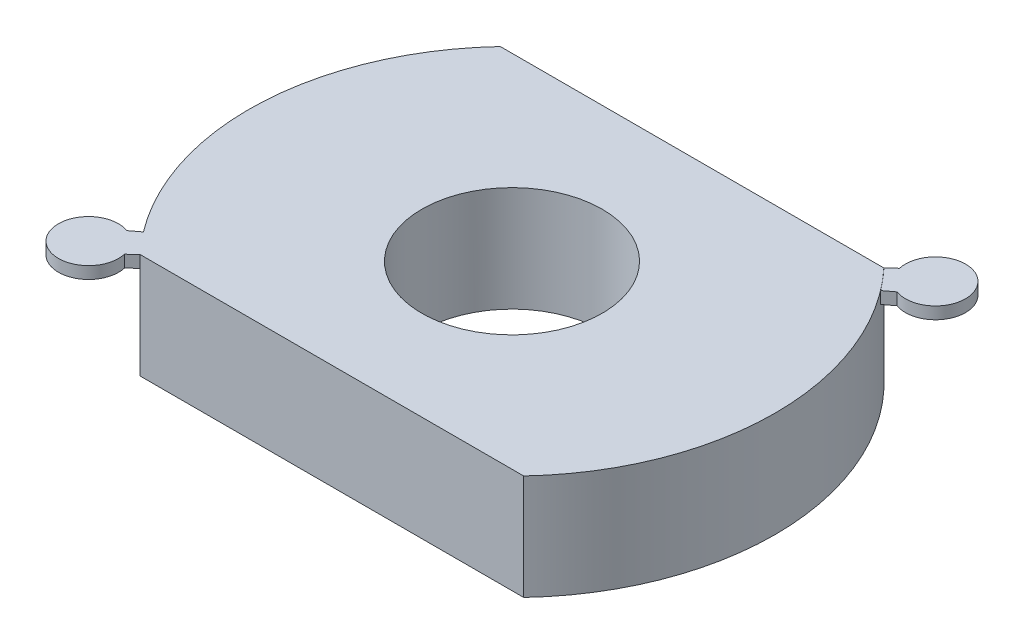
SolidWorks part; units mm, degrees
material "1345 Alloy"
ref_plane "Front Plane" through (0, 0, 0) normal (0, 0, 1) x (1, 0, 0)
ref_plane "Top Plane" through (0, 0, 0) normal (0, 1, 0) x (1, 0, 0)
ref_plane "Right Plane" through (0, 0, 0) normal (1, 0, 0) x (0, 0, -1)
sketch "Sketch1" plane through (0, 0, 0) normal (0, 1, 0) x (1, 0, 0)
  line L0 (-1712.4333, 578.2677) -> (-1658.0172, 559.892) construction
  line L1 (-1682.6566, 611.2885) -> (-1644.8226, 597.5438) construction
  line L2 (-1769.951, 660.0706) -> (-1712.4333, 741.8735) construction
  circle A0 centre (0, 0) radius 1750
  arc A3 (-1712.4333, 578.2677) -> (-1712.4333, 741.8735) centre (-1769.951, 660.0706) cw construction
  arc A4 (-1712.4333, 741.8735) -> (-1682.6566, 611.2885) centre (-1769.951, 660.0706) cw construction
extrude "Boss-Extrude1" add sketch "Sketch1" along normal blind 700
sketch "Sketch9" plane through (0, 0, 0) normal (0, -1, 0) x (1, 0, 0)
  line L1 (-2106.3119, -1198.0599) -> (2106.3119, -1198.0599)
  line L2 (-2106.3119, -1198.0599) -> (-2106.3119, 1198.0599)
  line L3 (-2106.3119, 1198.0599) -> (2106.3119, 1198.0599)
  line L4 (2106.3119, -1198.0599) -> (2106.3119, 1198.0599)
  line L5 (-2106.3119, -1198.0599) -> (2106.3119, 1198.0599) construction
  line L6 (-2106.3119, 1198.0599) -> (2106.3119, -1198.0599) construction
  line L7 (-2636.6179, -2082.9122) -> (2636.6179, -2082.9122)
  line L8 (-2636.6179, -2082.9122) -> (-2636.6179, 2082.9122)
  line L9 (-2636.6179, 2082.9122) -> (2636.6179, 2082.9122)
  line L10 (2636.6179, -2082.9122) -> (2636.6179, 2082.9122)
  line L11 (-2636.6179, -2082.9122) -> (2636.6179, 2082.9122) construction
  line L12 (-2636.6179, 2082.9122) -> (2636.6179, -2082.9122) construction
  point P0 (0, 0)
  point P6 (0, 0)
extrude "Cut-Extrude10" cut sketch "Sketch9" against normal through all both and the other way through all
sketch "Sketch3" plane through (0, 0, 0) normal (0, -1, 0) x (1, 0, 0)
  circle A0 centre (0, 0) radius 600
extrude "Cut-Extrude3" cut sketch "Sketch3" against normal through all both and the other way through all
shell "Shell1" thickness 1.5 removed face at (0, 0, 600)
sketch "Sketch12" plane through (0, 700, 0) normal (0, 1, 0) x (1, 0, 0)
  line L0 (-1275.7204, -1197.9305) -> (-1329.4274, -1248.3625)
  line L1 (-1275.7204, -1197.9305) -> (-1329.4274, -1248.3625)
  line L2 (-1456.8867, -1104.0663) -> (-1394.7434, -1056.9725)
  line L3 (-1212.6439, -1163.1539) -> (-1394.7434, -1056.9725) construction
  line L4 (-1329.4274, -1248.3625) -> (-1275.8583, -1198.0599) construction
  line L5 (1275.5989, -1198.0599) -> (-1275.5989, -1198.0599) construction
  line L6 (-1275.5989, 1198.0599) -> (1275.5989, -1198.0599) construction
  line L7 (0, 0) -> (-1750, 0) construction
  line L13 (0, 0) -> (0, 1750) construction
  line L14 (1212.6439, 1163.1539) -> (1394.7434, 1056.9725) construction
  line L15 (1329.4274, 1248.3625) -> (1275.8583, 1198.0599) construction
  line L16 (1275.7204, 1197.9305) -> (1329.4274, 1248.3625)
  line L17 (1275.7204, 1197.9305) -> (1329.4274, 1248.3625)
  line L18 (1456.8867, 1104.0663) -> (1394.7434, 1056.9725)
  arc A0 (-1275.5989, -1198.0599) -> (-1524.5473, -859.2179) centre (0, 0) cw
  arc A1 (-1275.7204, 1197.9305) -> (-1275.5989, 1198.0599) centre (0, 0) ccw construction
  arc A2 (-1329.4274, -1248.3625) -> (-1456.8867, -1104.0663) centre (-1524.5473, -1292.2737) cw
  arc A3 (-1275.7204, -1197.9305) -> (-1275.5989, -1198.0599) centre (0, 0) cw construction
  arc A4 (1275.8583, 1198.0599) -> (1394.7434, 1056.9725) centre (24.3381, 22.854) cw
  arc A6 (1329.4274, 1248.3625) -> (1456.8867, 1104.0663) centre (1524.5473, 1292.2737) cw
  arc M6 (-1275.5989, 1198.0599) -> (-1275.5989, -1198.0599) centre (0, 0) ccw
extrude "Boss-Extrude2" add sketch "Sketch12" against normal blind 80 contours A2 L0 L2 M6 region at (-1511.5348, 700, 1280.7775)
extrude "Boss-Extrude3" add sketch "Sketch12<6>" against normal blind 80 separate body contours A6 L17 A4 L18 region at (1511.5672, 700, -1280.8004)
sketch "Sketch12<6>" plane through (0, 700, 0) normal (0, 1, 0) x (1, 0, 0) same geometry as "Sketch12"
